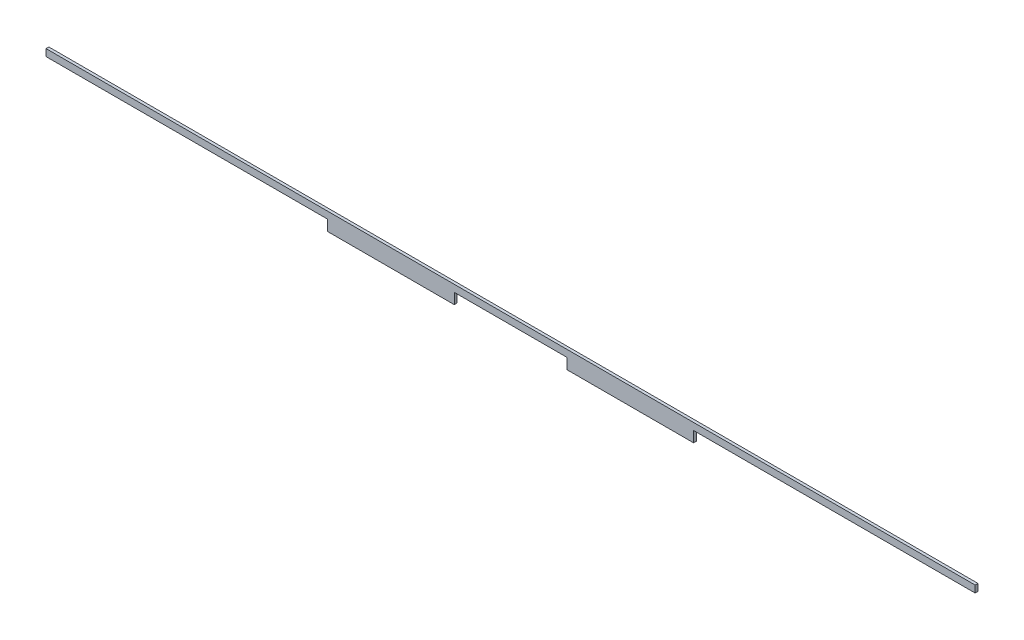
SolidWorks part; units mm, degrees
ref_plane "Front Plane" through (0, 0, 0) normal (0, 0, 1) x (1, 0, 0)
ref_plane "Top Plane" through (0, 0, 0) normal (0, 1, 0) x (1, 0, 0)
ref_plane "Right Plane" through (0, 0, 0) normal (1, 0, 0) x (0, 0, -1)
sketch "Sketch1" plane through (0, 0, 0) normal (0, 0, 1) x (1, 0, 0)
  line L0 (-250.1625, 15.1302) -> (739.8375, 15.1302)
  line L1 (304.8375, 7.7158) -> (184.8375, 7.7158)
  line L2 (244.8375, 7.7158) -> (244.8375, 15.1302) construction
  line L3 (739.8375, 15.1302) -> (739.8375, 7.7158)
  line L4 (-250.1625, 15.1302) -> (-250.1625, 7.7158)
  line L5 (-250.1625, 7.7158) -> (49.8375, 7.7158)
  line L6 (49.8375, 7.7158) -> (49.8375, -3.6812)
  line L7 (49.8375, -3.6812) -> (184.8375, -3.6812)
  line L8 (184.8375, -3.6812) -> (184.8375, 7.7158)
  line L9 (739.8375, 7.7158) -> (439.8375, 7.7158)
  line L10 (304.8375, -3.6812) -> (304.8375, 7.7158)
  line L11 (439.8375, -3.6812) -> (304.8375, -3.6812)
  line L12 (439.8375, 7.7158) -> (439.8375, -3.6812)
  point P5 (-144.6835, 7.7158)
  dimension "D1" = 60
  dimension "D2" = 135
  dimension "D3" = 300
extrude "Boss-Extrude1" add sketch "Sketch1" along normal blind 3 contours L7 L8 L1 L10 L11 L12 L9 L3 L0 L4 L5 L6
